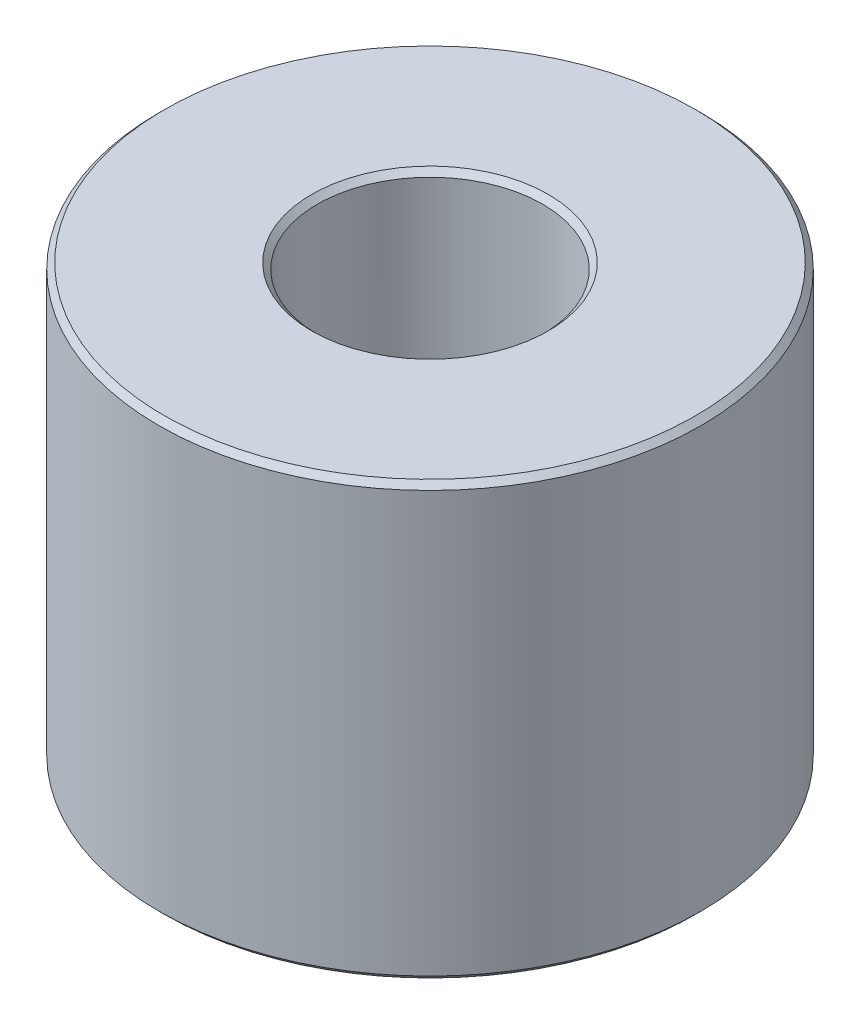
SolidWorks part; units mm, degrees
ref_plane "Front Plane" through (0, 0, 0) normal (0, 0, 1) x (1, 0, 0)
ref_plane "Top Plane" through (0, 0, 0) normal (0, 1, 0) x (1, 0, 0)
ref_plane "Right Plane" through (0, 0, 0) normal (1, 0, 0) x (0, 0, -1)
sketch "Sketch1" plane through (0, 0, 0) normal (0, 1, 0) x (1, 0, 0)
  circle A0 centre (0, 0) radius 45
  dimension "SLEEVE_OD" = 90
extrude "Boss-Extrude1" add sketch "Sketch1" along normal blind 71.703
sketch "Sketch2" plane through (0, 0, 0) normal (0, 1, 0) x (1, 0, 0)
  circle A0 centre (0, 0) radius 18.7053
  dimension "BORE_D" = 37.4106
extrude "Cut-Extrude1" cut sketch "Sketch2" along normal through all
chamfer "Chamfer1" distance 0.9385 angle 45 4 edges at (0, 71.703, 18.7053) (0, 0, 18.7053) (0, 0, 45) (0, 71.703, 45)
